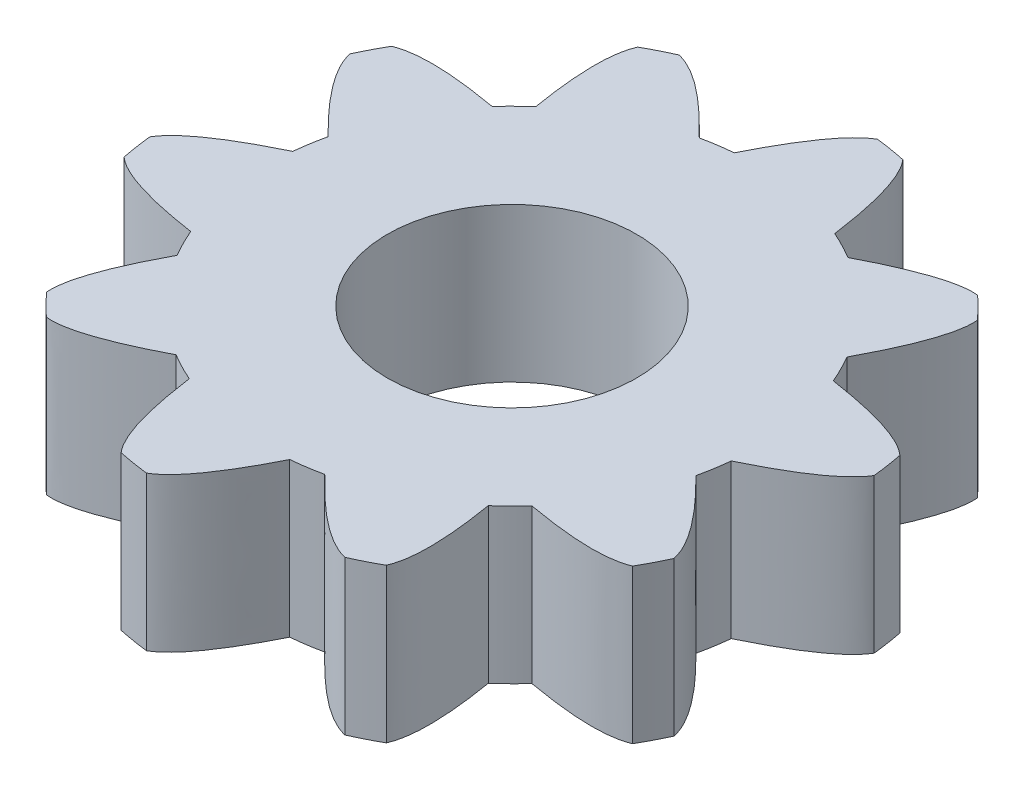
SolidWorks part; units mm, degrees
material "ABS"
ref_plane "Front Plane" through (0, 0, 0) normal (0, 0, 1) x (1, 0, 0)
ref_plane "Top Plane" through (0, 0, 0) normal (0, 1, 0) x (1, 0, 0)
ref_plane "Right Plane" through (0, 0, 0) normal (1, 0, 0) x (0, 0, -1)
sketch "Sketch1" plane through (0, 0, 0) normal (0, 1, 0) x (1, 0, 0)
  line L0 (4.0901, 6.8262) -> (6.8727, 4.0114) construction
  line L2 (5.4814, 5.4188) -> (7.6149, 7.5279) construction
  line L3 (7.6149, 7.5279) -> (7.7515, 7.6629)
  circle A0 centre (0, 0) radius 7.9577
  circle A1 centre (0, 0) radius 10.7077
  spline S0 degree 2 poles (6.8727, 4.0114) (10.0216, 9.9071) (4.0901, 6.8262) knots 0 0 0 1 1 1
  point P3 (4.0901, 6.8262)
  point P4 (6.8727, 4.0114)
  point P6 (7.2551, 7.8752)
  point P12 (3.2023, 7.285)
  point P14 (7.7515, 7.6629)
  point P15 (7.9581, 7.1641)
  point P16 (3.3638, 7.2119)
  dimension "D1" = 15.9155
  dimension "D4" = 3
  dimension "D5" = 1
  dimension "D2" = 4
  dimension "D3" = 1
extrude "Boss-Extrude4" add sketch "Sketch1" along normal blind 5 contours A0 | A0 S0 A1 region at (6.4406, 0, -6.367) region at (0, 0, 0)
pattern_circular "CirPattern6" count 10 every 36 about axis through (0, 5, 0) along (0, 1, 0) of "Boss-Extrude4"
sketch "Sketch2" plane through (0, 5, 0) normal (0, 1, 0) x (1, 0, 0)
  circle A0 centre (0, 0) radius 4.05
  dimension "D1" = 8.1
extrude "Cut-Extrude1" cut sketch "Sketch2" against normal blind 10 contours A0 region at (0, 5, 0)
sketch "Sketch3" plane through (0, 0, 0) normal (0, -1, 0) x (1, 0, 0)
equation "\"number-of-teeth\"= 10"
equation "\"gear-size\"= 4mm"
equation "\"circumference\"= \"number-of-teeth\" * ( ( 1 + \"space-between-teeth\" ) * \"gear-size\" )"
equation "\"space-between-teeth\"= .25"
equation "\"D1@Sketch1\" = \"circumference\" / pi"
equation "\"D2@Sketch1\"=\"gear-size\""
equation "\"gear-length\"= 3mm"
equation "\"D4@Sketch1\"=\"gear-length\""
equation "\"D5@Sketch1\"=\"gear-size\" * \"space-between-teeth\""
equation "\"D3@Sketch1\"=\"gear-size\" * \"space-between-teeth\""
equation "\"D1@CirPattern6\"=\"number-of-teeth\""
equation "\"D2@CirPattern6\"=360 / \"number-of-teeth\""
